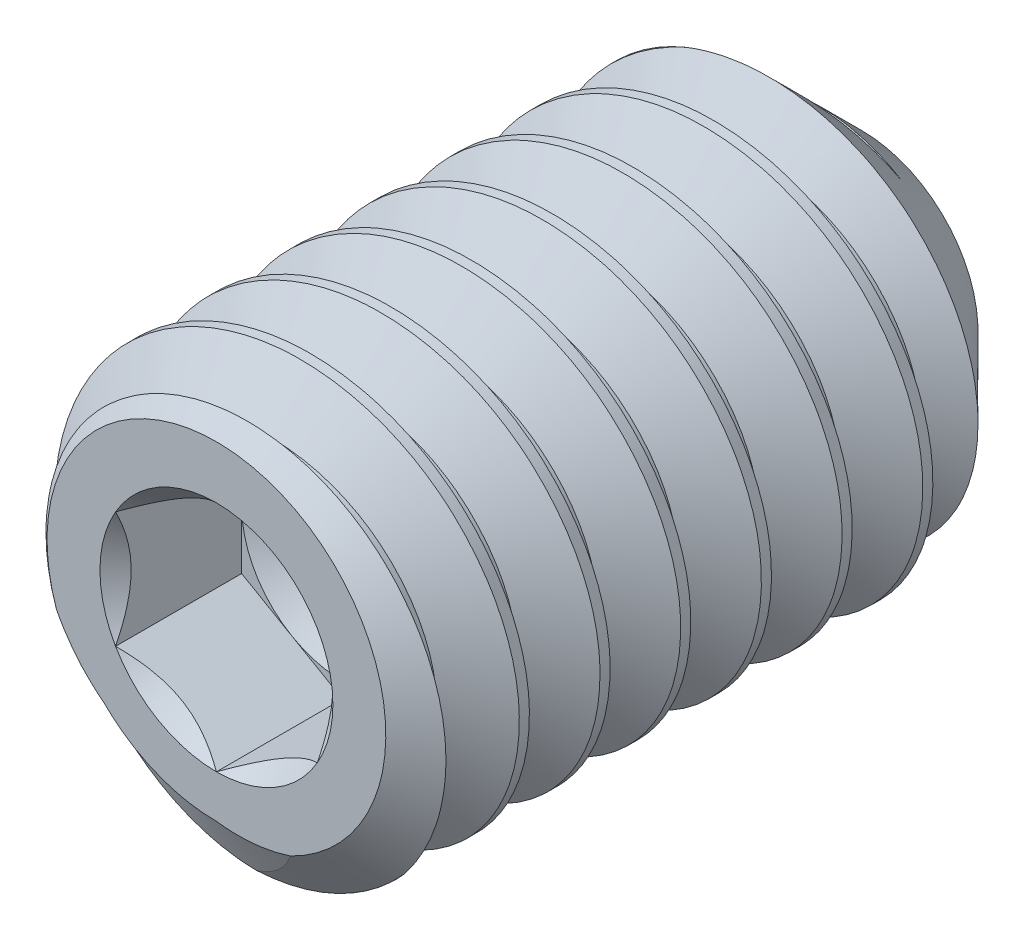
SolidWorks part; units mm, degrees
ref_plane "Front" through (0, 0, 0) normal (0, 0, 1) x (1, 0, 0)
ref_plane "Top" through (0, 0, 0) normal (0, 1, 0) x (1, 0, 0)
ref_plane "Right" through (0, 0, 0) normal (1, 0, 0) x (0, 0, -1)
sketch "Sketch22" plane through (0, 0, 0) normal (1, 0, 0) x (0, 0, -1)
  line L0 (-2.8321, 0) -> (-2.8321, 1.6662)
  line L1 (-2.8321, 1.6662) -> (-2.5404, 2.0828)
  line L2 (-2.5404, 2.0828) -> (2.5764, 2.0828)
  line L3 (2.5764, 2.0828) -> (3.5179, 1.1413)
  line L4 (3.5179, 1.1413) -> (2.8321, 0)
  line L5 (2.8321, 0) -> (-2.8321, 0)
  line L6 (2.8321, 0) -> (3.5179, 0) construction
  line L7 (3.5179, 0) -> (3.5179, 1.1413) construction
  line L8 (3.5179, -1.1413) -> (2.8321, 0) construction
  line L9 (-2.5404, -2.0828) -> (2.5764, -2.0828) construction
  dimension "Dia" = 4.1656
  dimension "Length" = 6.35
  dimension "D3" = 35
  dimension "D5" = 118
  dimension "D6" = 45
  dimension "D7" = 3.3325
revolve "Revolve1" add sketch "Sketch22" angle 360 about L6
ref_plane "Plane1" through (0, 0, -3.5179) normal (0, 0, 1) x (1, 0, 0)
sketch "Sketch27" plane through (0, 0, -3.5179) normal (0, 0, 1) x (1, 0, 0)
  circle A0 centre (0, 0) radius 2.0828 construction
  circle A1 centre (0, 0) radius 2.0828
curve "Helix/Spiral1" pitch 0.7937 height 7.1437 radius 2.0828 centre (0, 0, -3.5179) axis (0, 0, 1) start towards (0, 1, 0)
sketch "Sketch28" plane through (0, 0, 0) normal (1, 0, 0) x (0, 0, -1)
  line L0 (3.5179, 2.0828) -> (4.2124, 2.0828)
  line L1 (4.2124, 2.0828) -> (3.9148, 1.5672)
  line L2 (3.9148, 1.5672) -> (3.8155, 1.5672)
  line L3 (3.8155, 1.5672) -> (3.5179, 2.0828)
  line L4 (3.6667, 1.825) -> (4.0636, 1.825) construction
  line L6 (-2.5404, 2.0828) -> (2.5764, 2.0828) construction
  line L7 (3.5179, 3.4925) -> (3.5179, -3.4925) construction
  dimension "D1" = 0.0992
  dimension "D3" = 60
  dimension "D2" = 0.3969
sweep "Cut-Sweep2" cut profiles "Sketch28" path "Helix/Spiral1" align with end faces yes
sketch "Sketch23" plane through (0, 0, 2.8321) normal (0, 0, 1) x (1, 0, 0)
  line L1 (0, 1.1457) -> (-0.9922, 0.5728)
  line L2 (-0.9922, 0.5728) -> (-0.9922, -0.5728)
  line L3 (-0.9922, -0.5728) -> (0, -1.1457)
  line L4 (0, -1.1457) -> (0.9922, -0.5728)
  line L5 (0.9922, -0.5728) -> (0.9922, 0.5728)
  line L6 (0.9922, 0.5728) -> (0, 1.1457)
  circle A0 centre (0, 0) radius 0.9922 construction
  dimension "Hex" = 1.9844
extrude "Cut-Extrude10" cut sketch "Sketch23" against normal blind 1.2402
sketch "Sketch24" plane through (0, 0, 2.8321) normal (0, 0, 1) x (1, 0, 0)
  circle A0 centre (0, 0) radius 1.1457
extrude "Cut-Extrude11" cut sketch "Sketch24" against normal through all draft 45
sketch "Sketch26" plane through (0, 0, 1.5919) normal (0, 0, 1) x (1, 0, 0)
  circle A0 centre (0, 0) radius 0.9922 construction
  circle A1 centre (0, 0) radius 0.9922
extrude "Cut-Extrude12" cut sketch "Sketch26" against normal through all draft 60
sketch "Sketch30" plane through (0, 0, 0) normal (1, 0, 0) x (0, 0, -1)
  line L0 (-2.5404, 2.0828) -> (2.5764, 2.0828) construction
  line L1 (-2.8321, 0) -> (-2.8321, 1.6662) construction
  line L2 (3.5179, 0) -> (3.5179, 1.1413) construction
  line L3 (-2.5404, -2.0828) -> (2.5764, -2.0828) construction
  point P0 (-2.8321, 2.0828)
  point P1 (3.5179, 2.0828)
  point P2 (3.5179, -2.0828)
  point P11 (1.5335, -2.0828)
  dimension "D1" = 1.9844
sketch "Sketch31" plane through (0, 0, 0) normal (1, 0, 0) x (0, 0, -1)
  line L2 (2.8321, 0) -> (3.5179, -1.1413)
  line L3 (3.5179, 1.1413) -> (2.8321, 0)
equation "\"D7@Sketch22\"=\"Dia@Sketch22\"*.8"
equation "\"D1@Sketch28\" = \"D4@Helix/Spiral1\" * .125"
equation "\"D3@Helix/Spiral1\" = \"Length@Sketch22\" + \"D4@Helix/Spiral1\""
equation "\"D1@Sketch30\" = \"D4@Helix/Spiral1\" * 2.5"
equation "\"hex Depth@Cut-Extrude10\" = \"Hex@Sketch23\" * .625"
equation "\"D2@Sketch28\" = \"D4@Helix/Spiral1\" * .5"
